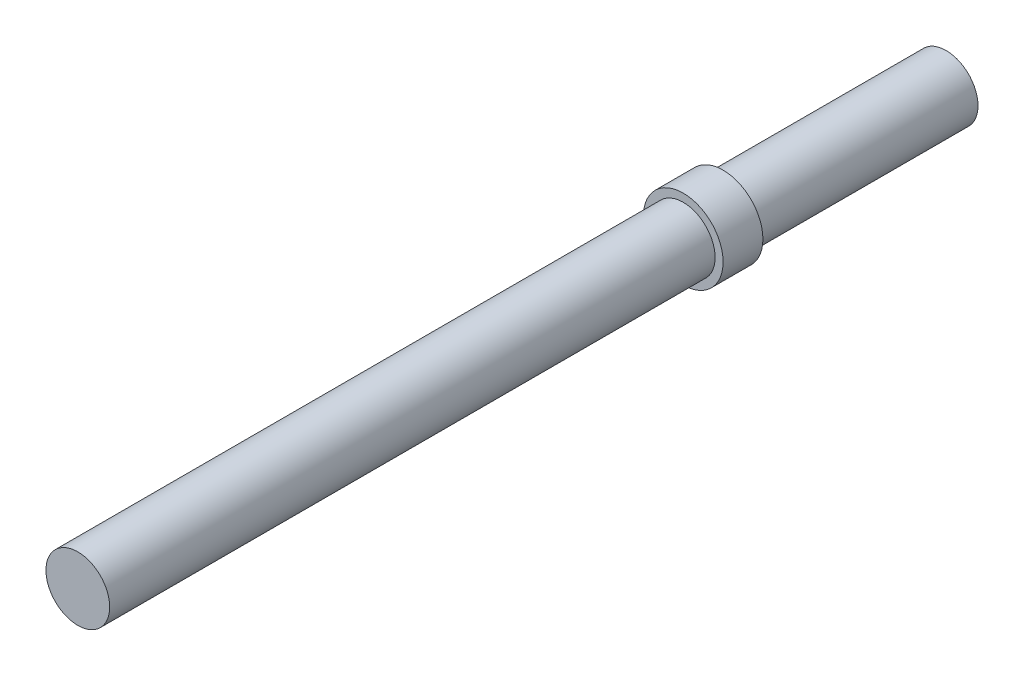
SolidWorks part; units mm, degrees
ref_plane "Alzado" through (0, 0, 0) normal (0, 0, 1) x (1, 0, 0)
ref_plane "Planta" through (0, 0, 0) normal (0, 1, 0) x (1, 0, 0)
ref_plane "Vista lateral" through (0, 0, 0) normal (1, 0, 0) x (0, 0, -1)
sketch "Croquis1" plane through (0, 0, 0) normal (0, 0, 1) x (1, 0, 0)
  circle A0 centre (0, 0) radius 4
  dimension "D1" = 8
extrude "Saliente-Extruir1" add sketch "Croquis1" along normal mid plane 109
ref_plane "Plano2" through (3, 0, 0) normal (1, 0, 0) x (0, 0, -1)
ref_plane "Plano3" through (0, 0, -26.5) normal (0, 0, 1) x (1, 0, 0)
sketch "Croquis2" plane through (0, 0, -26.5) normal (0, 0, 1) x (1, 0, 0)
  circle A0 centre (0, 0) radius 5
  dimension "D1" = 10
extrude "Saliente-Extruir2" add sketch "Croquis2" along normal blind 5
